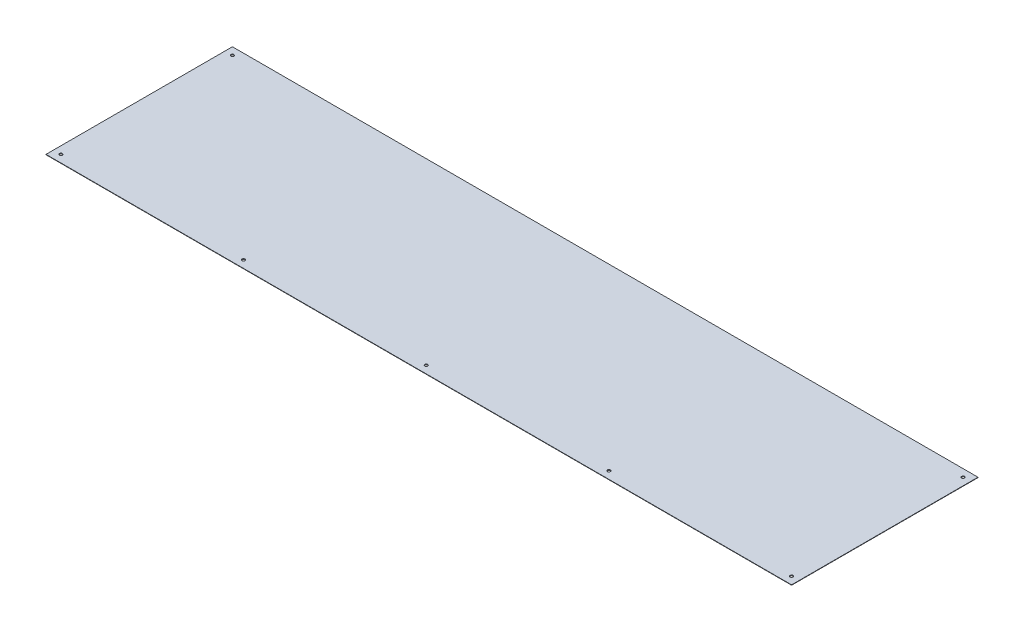
SolidWorks part; units mm, degrees
ref_plane "Front Plane" through (0, 0, 0) normal (0, 0, 1) x (1, 0, 0)
ref_plane "Top Plane" through (0, 0, 0) normal (0, 1, 0) x (1, 0, 0)
ref_plane "Right Plane" through (0, 0, 0) normal (1, 0, 0) x (0, 0, -1)
sketch "Sketch1" plane through (0, 0, 0) normal (0, 1, 0) x (1, 0, 0)
  line L1 (-1000, 250) -> (1000, 250)
  line L2 (-1000, 250) -> (-1000, -250)
  line L3 (-1000, -250) -> (1000, -250)
  line L4 (1000, 250) -> (1000, -250)
  line L5 (-1000, 250) -> (1000, -250) construction
  line L6 (-1000, -250) -> (1000, 250) construction
  line L7 (0, -230) -> (980, -230) construction
  line L8 (980, 230) -> (980, -230) construction
  line L10 (-980, -230) -> (0, -230) construction
  line L11 (-980, 230) -> (980, 230) construction
  line L12 (-1000, 230) -> (1000, 230) construction
  line L13 (-980, 230) -> (-980, -230) construction
  circle A0 centre (-980, -230) radius 3
  circle A1 centre (980, -230) radius 3
  circle A2 centre (0, -230) radius 3
  circle A3 centre (-490, -230) radius 3
  circle A4 centre (490, -230) radius 3
  circle A5 centre (980, 230) radius 3
  circle A6 centre (-980, 230) radius 3
  point P0 (0, 0)
  dimension "D3" = 6
  dimension "D4" = 6
  dimension "D5" = 6
  dimension "D6" = 6
  dimension "D7" = 6
  dimension "D8" = 6
  dimension "D9" = 6
  dimension "D1" = 2000
  dimension "D2" = 500
extrude "Boss-Extrude1" add sketch "Sketch1" along normal blind 1
chamfer "Chamfer1" distance 1 angle 45 7 edges at (980, 1, -227) (980, 1, 233) (490, 1, 233) (0, 1, 233) (-490, 1, 233) (-980, 1, 233) (-980, 1, -227)
